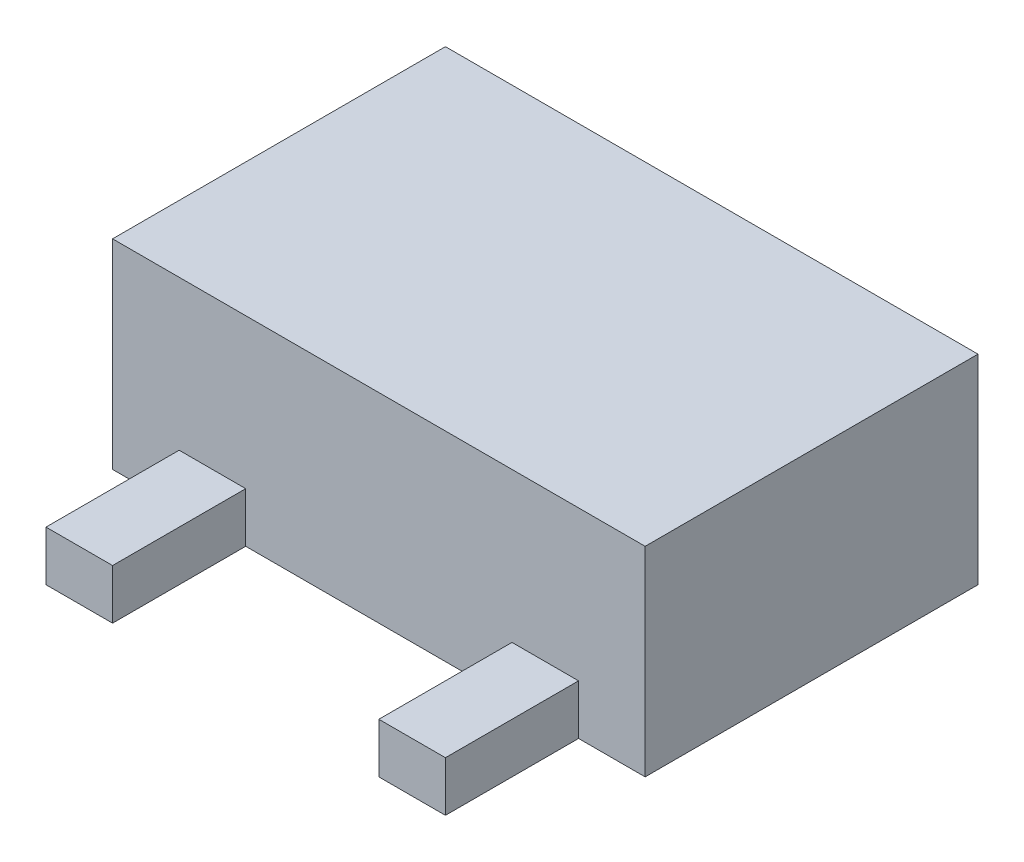
SolidWorks part; units mm, degrees
ref_plane "Front Plane" through (0, 0, 0) normal (0, 0, 1) x (1, 0, 0)
ref_plane "Top Plane" through (0, 0, 0) normal (0, 1, 0) x (1, 0, 0)
ref_plane "Right Plane" through (0, 0, 0) normal (1, 0, 0) x (0, 0, -1)
sketch "BaseS" plane through (0, 0, 0) normal (0, 1, 0) x (1, 0, 0)
  line L1 (-0.8, 0.5) -> (0.8, 0.5)
  line L2 (-0.8, 0.5) -> (-0.8, -0.5)
  line L3 (-0.8, -0.5) -> (0.8, -0.5)
  line L4 (0.8, 0.5) -> (0.8, -0.5)
  line L5 (-0.8, 0.5) -> (0.8, -0.5) construction
  line L6 (-0.8, -0.5) -> (0.8, 0.5) construction
  point P0 (0, 0)
  dimension "Width" = 1.6
  dimension "Length" = 1
extrude "Base" add sketch "BaseS" along normal blind 0.6
sketch "LegS" plane through (0, 0, 0) normal (0, 1, 0) x (1, 0, 0)
  line L0 (0.8, 0.5) -> (-0.8, 0.5) construction
  line L1 (-0.1, 0.5) -> (0.1, 0.5)
  line L2 (-0.1, 0.5) -> (-0.1, 0.9)
  line L3 (-0.1, 0.9) -> (0.1, 0.9)
  line L4 (0.1, 0.5) -> (0.1, 0.9)
  point P6 (0, 0.5)
  dimension "Length" = 0.4
  dimension "Width" = 0.2
extrude "Leg" add sketch "LegS" along normal blind 0.15
sketch "SideLegS" plane through (0, 0, 0) normal (0, 1, 0) x (1, 0, 0)
  line L0 (-0.8, -0.5) -> (0.8, -0.5) construction
  line L1 (-0.6, -0.5) -> (-0.4, -0.5)
  line L2 (-0.6, -0.5) -> (-0.6, -0.9)
  line L3 (-0.6, -0.9) -> (-0.4, -0.9)
  line L4 (-0.4, -0.5) -> (-0.4, -0.9)
  line L5 (-0.1, 0.5) -> (-0.1, 0.9) construction
  line L6 (-0.1, 0.5) -> (0.1, 0.5) construction
  line L7 (-0.8, 0.5) -> (-0.8, -0.5) construction
  dimension "D1" = 0.2
extrude "SideLeg" add sketch "SideLegS" along normal up to surface (0.15 mm away) up to face at (0, 0.15, -0.7)
mirror "SLHM" about plane through (0, 0, 0) normal (1, 0, 0) of "SideLeg"
